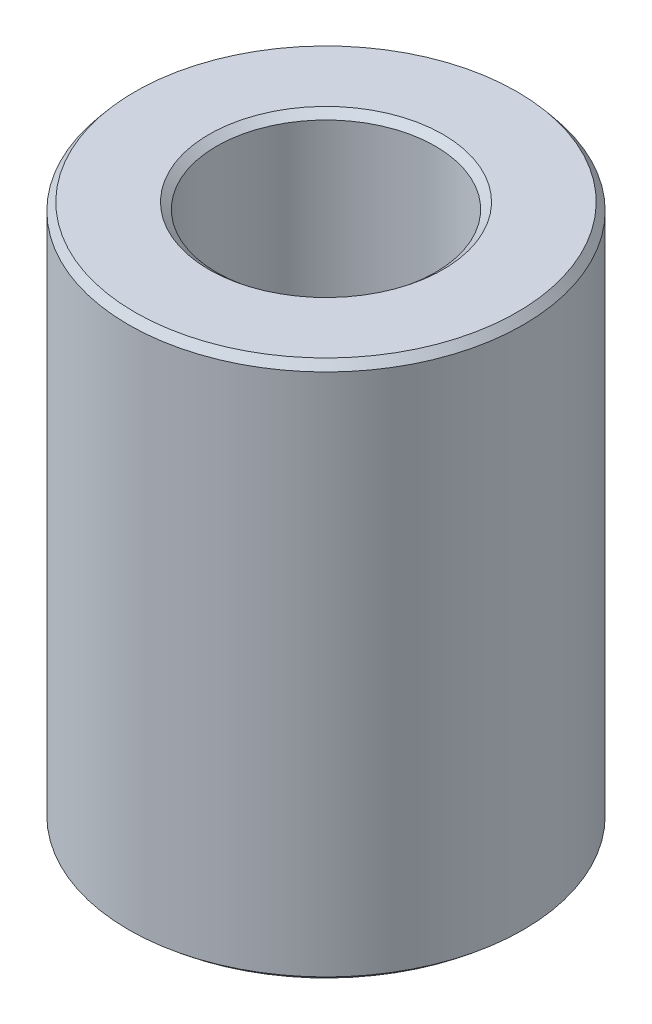
SolidWorks part; units mm, degrees
ref_plane "Front Plane" through (0, 0, 0) normal (0, 0, 1) x (1, 0, 0)
ref_plane "Top Plane" through (0, 0, 0) normal (0, 1, 0) x (1, 0, 0)
ref_plane "Right Plane" through (0, 0, 0) normal (1, 0, 0) x (0, 0, -1)
sketch "Sketch1" plane through (0, 0, 0) normal (0, 1, 0) x (1, 0, 0)
  circle A0 centre (0, 0) radius 40
  dimension "SLEEVE_OD" = 80
extrude "Boss-Extrude1" add sketch "Sketch1" along normal blind 108.9922
sketch "Sketch2" plane through (0, 0, 0) normal (0, 1, 0) x (1, 0, 0)
  circle A0 centre (0, 0) radius 22.1664
  dimension "BORE_D" = 44.3327
extrude "Cut-Extrude1" cut sketch "Sketch2" along normal through all
chamfer "Chamfer1" distance 1.5537 angle 39.58 4 edges at (0, 108.9922, 22.1664) (0, 0, 22.1664) (0, 0, 40) (0, 108.9922, 40) first distance on face at (0, 108.9922, 22.1664) first distance on face at (0, 0, 22.1664) first distance on face at (0, 108.9922, 40)
